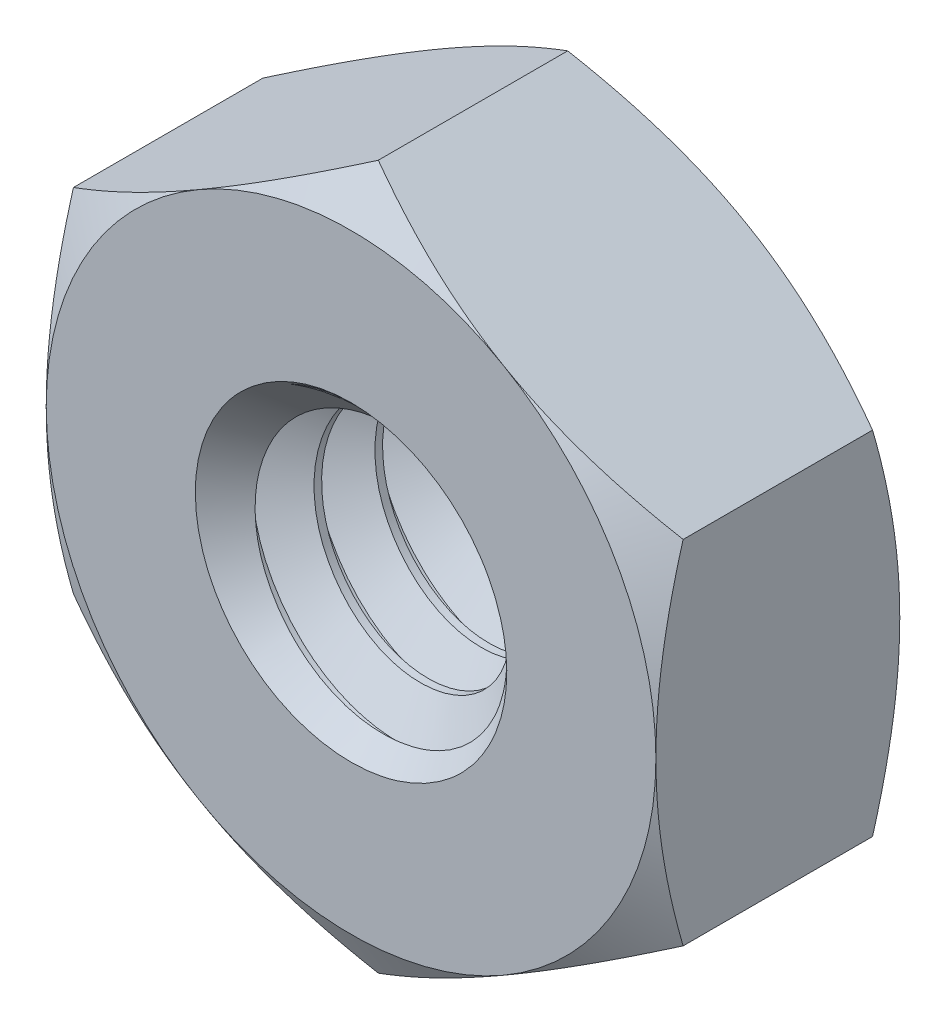
SolidWorks part; units mm, degrees
ref_plane "Front Plane" through (0, 0, 0) normal (0, 0, 1) x (1, 0, 0)
ref_plane "Top Plane" through (0, 0, 0) normal (0, 1, 0) x (1, 0, 0)
ref_plane "Right Plane" through (0, 0, 0) normal (1, 0, 0) x (0, 0, -1)
sketch "Sketch1" plane through (0, 0, 0) normal (1, 0, 0) x (0, 0, -1)
  line L0 (-0.8, 0) -> (0.8, 0) construction
  line L1 (-0.8, -2) -> (-0.8, 2) construction
  line L2 (0.8, -2) -> (0.8, 2) construction
  line L3 (-0.8, -1) -> (-0.8, 1) construction
  line L4 (-1.175, 1.0433) -> (-0.975, 0.6969) construction
  line L5 (-0.975, 0.6969) -> (-0.775, 1.0433) construction
  line L6 (-0.775, 1.0433) -> (-1.175, 1.0433) construction
  line L7 (-1.1625, 1.0217) -> (-0.7875, 1.0217) construction
  line L8 (-1.15, 1) -> (-0.8, 1) construction
  line L9 (-1, 0.7402) -> (-0.95, 0.7402) construction
  line L10 (-0.975, 0.7402) -> (-0.975, 0.6969) construction
  line L11 (-0.975, 1.0433) -> (-0.975, 1) construction
  point P4 (0, 0)
  point P7 (-0.8, 0)
  point P11 (0.8, 0)
  point P14 (-0.8, 0)
  point P26 (-0.975, 1.0217)
  point P27 (-0.8, -1)
  dimension "Height" = 1.6
  dimension "Width" = 4
  dimension "Thread OD" = 2
  dimension "D1" = 60
  dimension "Pitch" = 0.4
  dimension "D2" = 0.05
sketch "Sketch2" plane through (0, 0, 0) normal (0, 0, 1) x (1, 0, 0)
  line L1 (0, 2.3094) -> (-2, 1.1547)
  line L2 (-2, 1.1547) -> (-2, -1.1547)
  line L3 (-2, -1.1547) -> (0, -2.3094)
  line L4 (0, -2.3094) -> (2, -1.1547)
  line L5 (2, -1.1547) -> (2, 1.1547)
  line L6 (2, 1.1547) -> (0, 2.3094)
  circle A0 centre (0, 0) radius 2 construction
  circle A1 centre (0, 0) radius 1
extrude "Boss-Extrude1" add sketch "Sketch2" along normal up to vertex (0.8 mm away) and the other way up to vertex (0.8 mm away) up to point (0, -2, 0.8) other way up to point (0, -2, -0.8)
sketch "Sketch3" plane through (0, 0, 0.8) normal (0, 0, 1) x (1, 0, 0)
  circle A0 centre (0, 0) radius 2
extrude "Cut-Extrude1" cut sketch "Sketch3" against normal through all draft 60 flip side to cut
mirror "Mirror1" about plane through (0, 0, 0) normal (0, 0, 1) of "Cut-Extrude1"
ref_axis "Center Axis 1" through (0, 0, -10.9016) along (0, 0, 1)
ref_plane "Contact Plane 1" through (0, 0, 0.8) normal (0, 0, 1) x (1, 0, 0)
ref_plane "Contact Plane 2" through (0, 0, -0.8) normal (0, 0, -1) x (-1, 0, 0)
sketch "Sketch4" plane through (0, 0, 0) normal (1, 0, 0) x (0, 0, -1)
  line L1 (-1.1625, 1.0217) -> (-1, 0.7402)
  line L2 (-1, 0.7402) -> (-0.95, 0.7402)
  line L3 (-0.95, 0.7402) -> (-0.7875, 1.0217)
  line L4 (-1.1625, 1.0217) -> (-0.7875, 1.0217) construction
  line L5 (-1.1625, 1.0217) -> (-0.7875, 1.0217)
sketch "Sketch5" plane through (0, 0, 0.8) normal (0, 0, 1) x (1, 0, 0)
  circle A0 centre (0, 0) radius 1 construction
  circle A1 centre (0, 0) radius 1
curve "Helix/Spiral1" pitch 0.4 height 2 radius 1 centre (0, 0, 0.8) axis (0, 0, -1) start towards (0, 1, 0)
sweep "Sweep1" add profiles "Sketch4" path "Helix/Spiral1"
sketch "Sketch6" plane through (0, 0, 0.8) normal (0, 0, 1) x (1, 0, 0)
  circle A1 centre (0, 0) radius 1.0217
extrude "Cut-Extrude2" cut sketch "Sketch6" along normal through all and the other way through all draft 45
sketch "Sketch7" plane through (0, 0, -0.8) normal (0, 0, -1) x (-1, 0, 0)
  circle A1 centre (0, 0) radius 1.0217
  circle A2 centre (0, 0) radius 1.0217
  dimension "D1" = 0
extrude "Cut-Extrude3" cut sketch "Sketch7" along normal through all and the other way through all draft 45
equation "\"D2@Sketch1\"=\"Pitch@Sketch1\"/8"
equation "\"D4@Helix/Spiral1\"=\"Pitch@Sketch1\""
equation "\"D3@Helix/Spiral1\"=\"Height@Sketch1\"+\"Pitch@Sketch1\""
